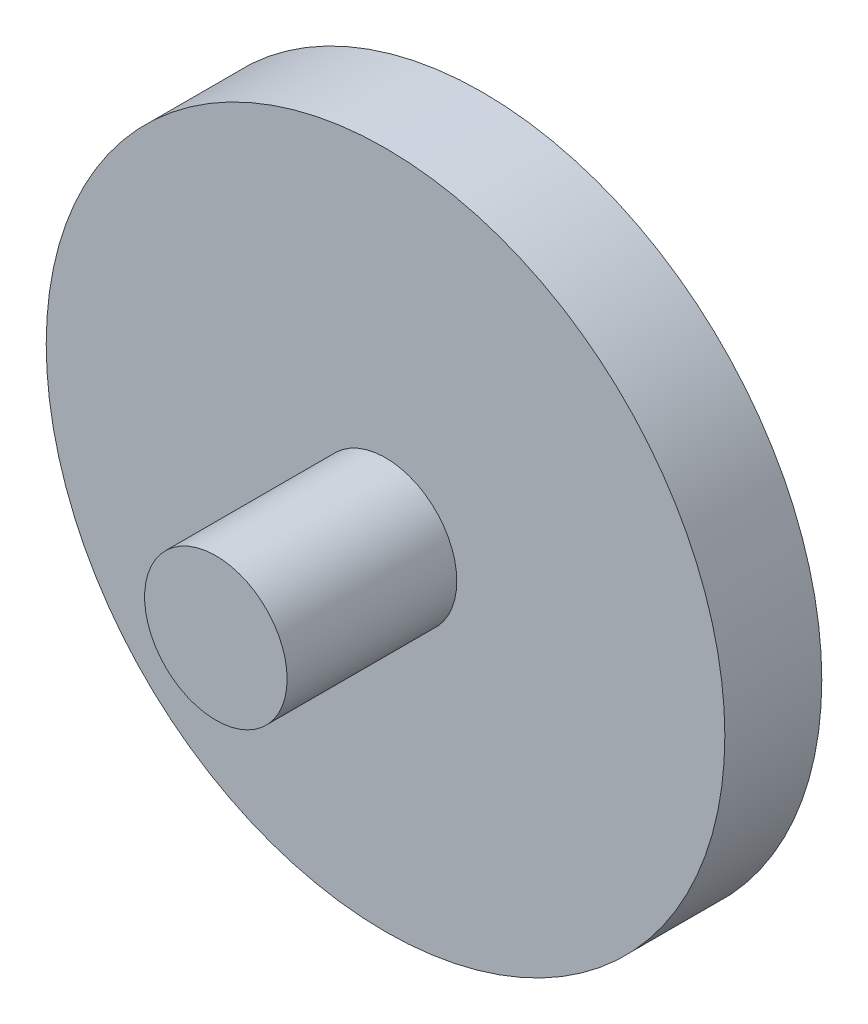
SolidWorks part; units mm, degrees
ref_plane "Front Plane" through (0, 0, 0) normal (0, 0, 1) x (1, 0, 0)
ref_plane "Top Plane" through (0, 0, 0) normal (0, 1, 0) x (1, 0, 0)
ref_plane "Right Plane" through (0, 0, 0) normal (1, 0, 0) x (0, 0, -1)
sketch "Sketch1" plane through (0, 0, 0) normal (0, 0, 1) x (1, 0, 0)
  circle A0 centre (0, 0) radius 14
  dimension "D1" = 28
extrude "Boss-Extrude1" add sketch "Sketch1" along normal blind 4
sketch "Sketch2" plane through (0, 0, 4) normal (0, 0, 1) x (1, 0, 0)
  circle A0 centre (0, 0) radius 2.94
  dimension "D1" = 5.88
extrude "Boss-Extrude2" add sketch "Sketch2" along normal blind 7
sketch "Sketch4" plane through (0, 0, 0) normal (0, 0, -1) x (-1, 0, 0)
  circle A0 centre (0, 0) radius 11
  dimension "D1" = 22
extrude "Cut-Extrude1" cut sketch "Sketch4" against normal blind 1
fillet "Fillet1" radius 0.5 2 edges at (-11, 0, 0) (-11, 0, 1)
